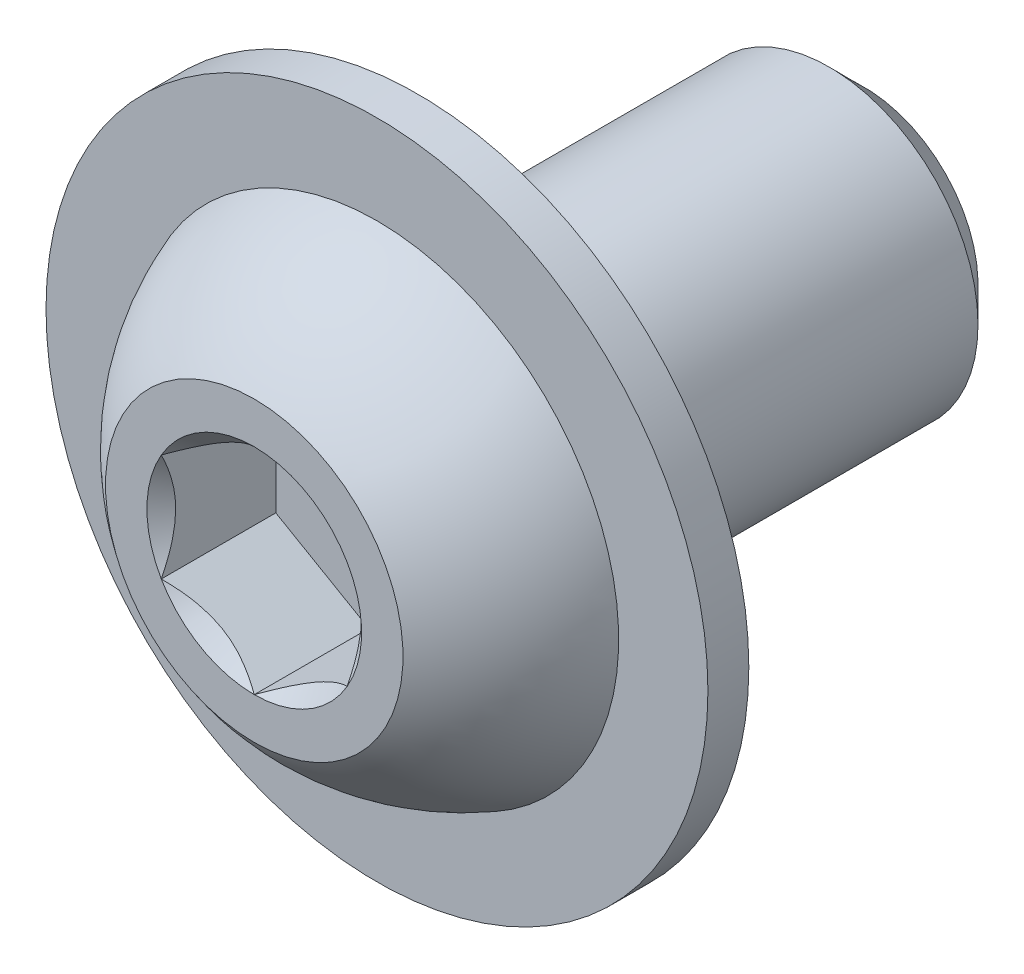
SolidWorks part; units mm, degrees
material "AISI 304"
ref_plane "Front" through (0, 0, 0) normal (0, 0, 1) x (1, 0, 0)
ref_plane "Top" through (0, 0, 0) normal (0, 1, 0) x (1, 0, 0)
ref_plane "Right" through (0, 0, 0) normal (1, 0, 0) x (0, 0, -1)
sketch "Sketch1" plane through (0, 0, 0) normal (1, 0, 0) x (0, 0, -1)
  line L2 (4.4, 4) -> (16.4, 4)
  line L3 (16.4, 4) -> (16.4, 0)
  line L4 (16.4, 0) -> (4.4, 0)
  line L6 (3.3, 6.5) -> (4.4, 6.5) construction
  line L7 (16.4, 4) -> (16.4, -4) construction
  line L8 (0, 0) -> (4.4, 0) construction
  line L9 (4.4, 6.5) -> (4.4, -6.5) construction
  line L11 (4.4, 4) -> (4.4, 0)
  line L13 (0, 2.5) -> (0, -2.5) construction
  line L14 (0, 2.5) -> (0, 4) construction
  line L15 (3.3, 6.5) -> (3.3, 8.9) construction
  line L16 (3.3, 8.9) -> (4.4, 8.9) construction
  line L17 (4.4, 8.9) -> (4.4, 6.5) construction
  line L18 (4.4, 8.9) -> (4.4, -8.9) construction
  arc A3 (0, 4) -> (3.3, 6.5) centre (5.6273, 0) cw construction
  dimension "D1" = 1.1
revolve "Revolve1" add sketch "Sketch1" angle 360 mid plane about L4
sketch "Sketch3" plane through (0, 0, -16.4) normal (0, 0, -1) x (-1, 0, 0)
  circle A0 centre (0, 0) radius 4
curve "Helix/Spiral1" pitch 1.25 height 13.25 turns 10.6
sketch "Sketch2" plane through (0, 0, 0) normal (1, 0, 0) x (0, 0, -1)
  line L0 (16.4, 4) -> (17.4937, 4)
  line L1 (17.4937, 4) -> (17.025, 3.1881)
  line L2 (17.025, 3.1881) -> (16.8687, 3.1881)
  line L3 (16.8687, 3.1881) -> (16.4, 4)
  line L4 (16.6344, 3.5941) -> (17.2594, 3.5941) construction
  dimension "D1" = 60
  dimension "D2" = 0.1562
  dimension "D3" = 0.625
chamfer "Chamfer1" distance 0.9375 angle 45 1 edges at (0, 4, -16.4)
sweep "Cut-Sweep1" [suppressed] cut profiles "Sketch2" path "Helix/Spiral1"
sketch "Sketch7" plane through (0, 0, 0) normal (1, 0, 0) x (0, 0, -1)
  line L6 (3.3, 6.5) -> (4.4, 6.5) construction
  line L8 (0, 0) -> (4.4, 0) construction
  line L11 (4.4, 6.5) -> (4.4, -6.5) construction
  line L12 (3.3, 6.5) -> (4.4, 6.5)
  line L13 (0, 0) -> (4.4, 0)
  line L14 (0, 2.5) -> (0, -2.5) construction
  line L15 (4.4, 6.5) -> (4.4, 0)
  line L16 (0, 4) -> (0, 0)
  arc A2 (3.3, 6.5) -> (0, 4) centre (5.6273, 0) ccw construction
  arc A3 (3.3, 6.5) -> (0, 4) centre (5.6273, 0) ccw
revolve "Revolve2" add sketch "Sketch7" angle 360 mid plane about L13
sketch "Sketch11" plane through (0, 0, -4.4) normal (0, 0, -1) x (-1, 0, 0)
  circle A0 centre (0, 0) radius 8.9
extrude "Boss-Extrude3" add sketch "Sketch11" against normal up to vertex (1.1 mm away) up to point (0, 6.5, -3.3)
sketch "Sketch5" plane through (0, 0, 0) normal (0, 0, 1) x (1, 0, 0)
  line L1 (2.5, -1.4434) -> (2.5, 1.4434)
  line L2 (2.5, 1.4434) -> (0, 2.8868)
  line L3 (0, 2.8868) -> (-2.5, 1.4434)
  line L4 (-2.5, 1.4434) -> (-2.5, -1.4434)
  line L5 (-2.5, -1.4434) -> (0, -2.8868)
  line L6 (0, -2.8868) -> (2.5, -1.4434)
  circle A0 centre (0, 0) radius 2.5 construction
extrude "Cut-Extrude2" cut sketch "Sketch5" against normal blind 3.08
sketch "Sketch6" plane through (0, 0, 0) normal (0, 0, 1) x (1, 0, 0)
  circle A0 centre (0, 0) radius 2.8868
extrude "Cut-Extrude3" cut sketch "Sketch6" against normal blind 3.08 draft 45
sketch "Sketch9" [suppressed] plane through (0, 0, -4.4) normal (0, 0, 1) x (1, 0, 0)
  circle A2 centre (0, 0) radius 4
extrude "Boss-Extrude2" [suppressed] add sketch "Sketch9" against normal offset from surface (6.35 mm away) 31.75
sketch "Sketch10" plane through (0, 0, 0) normal (1, 0, 0) x (0, 0, -1)
  line L0 (16.4, 4) -> (16.4, -4) construction
  point P0 (14.525, -4)
  dimension "D1" = 1.875
equation "\"D3@Helix/Spiral1\" = \"Lg@Sketch1\" + \"D4@Helix/Spiral1\""
equation "\"D2@Sketch2\" = \"D4@Helix/Spiral1\" * .125"
equation "\"D3@Sketch2\" = \"D4@Helix/Spiral1\" * .5"
equation "\"D1@Chamfer1\" = \"D4@Helix/Spiral1\" * .75"
equation "\"D1@Cut-Extrude2\" = \"Head Ht@Sketch1\" * .7"
equation "\"D1@Sketch1\" = \"Head Ht@Sketch1\" * .25"
equation "\"D1@Sketch10\" = \"D4@Helix/Spiral1\" * 1.5"
equation "\"D1@Cut-Extrude3\" = \"D1@Cut-Extrude2\""
